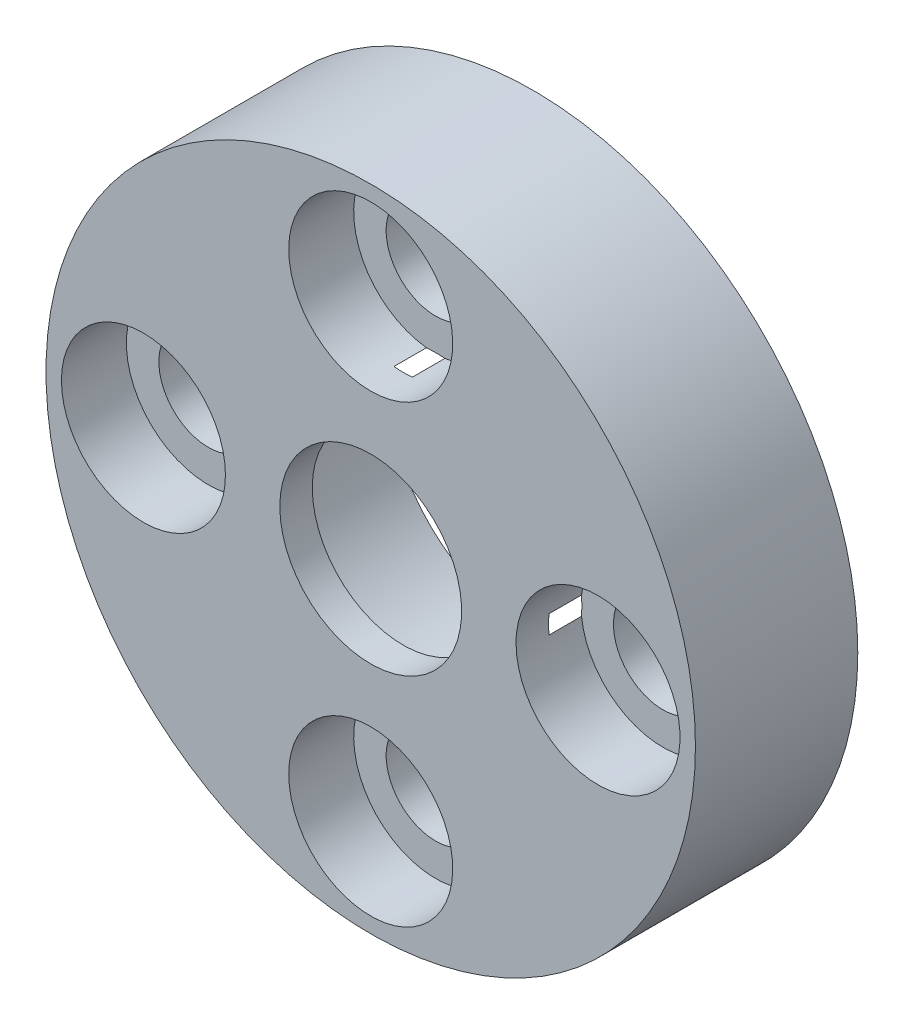
SolidWorks part; units mm, degrees
ref_plane "Front Plane" through (0, 0, 0) normal (0, 0, 1) x (1, 0, 0)
ref_plane "Top Plane" through (0, 0, 0) normal (0, 1, 0) x (1, 0, 0)
ref_plane "Right Plane" through (0, 0, 0) normal (1, 0, 0) x (0, 0, -1)
sketch "Sketch1" plane through (0, 0, 0) normal (0, 0, 1) x (1, 0, 0)
  circle A2 centre (-7, 0) radius 1.525
  circle A4 centre (0, -7) radius 1.525
  circle A6 centre (7, 0) radius 1.525
  circle A8 centre (0, 7) radius 1.525
  circle A9 centre (0, 0) radius 10
extrude "Boss-Extrude1" add sketch "Sketch1" along normal blind 5
sketch "Sketch2" plane through (0, 0, 0) normal (0, 0, -1) x (-1, 0, 0)
  circle A1 centre (0, 0) radius 4.5
  dimension "D1" = 9
extrude "Cut-Extrude1" cut sketch "Sketch2" against normal offset from surface (4 mm away) 1 up to face at (1.525, 7, 5)
sketch "Sketch3" plane through (0, 0, 4) normal (0, 0, -1) x (-1, 0, 0)
  circle A0 centre (0, 0) radius 2.8
  dimension "D1" = 5.6
extrude "Cut-Extrude2" cut sketch "Sketch3" against normal through all
sketch "Sketch5" plane through (0, 0, 5) normal (0, 0, -1) x (-1, 0, 0)
  circle A0 centre (7, 0) radius 1.525 construction
  circle A1 centre (0, -7) radius 1.525 construction
  circle A2 centre (-7, 0) radius 1.525 construction
  circle A3 centre (0, 7) radius 1.525 construction
  circle A4 centre (7, 0) radius 1.525
  circle A5 centre (0, -7) radius 1.525
  circle A6 centre (-7, 0) radius 1.525
  circle A7 centre (0, 7) radius 1.525
  circle A8 centre (7, 0) radius 2.525
  circle A9 centre (0, -7) radius 2.525
  circle A10 centre (-7, 0) radius 2.525
  circle A11 centre (0, 7) radius 2.525
  dimension "D1" = 1
extrude "Cut-Extrude4" cut sketch "Sketch5" along normal offset from surface (2 mm away) 3 up to face at (-4.5, 0, 0)
